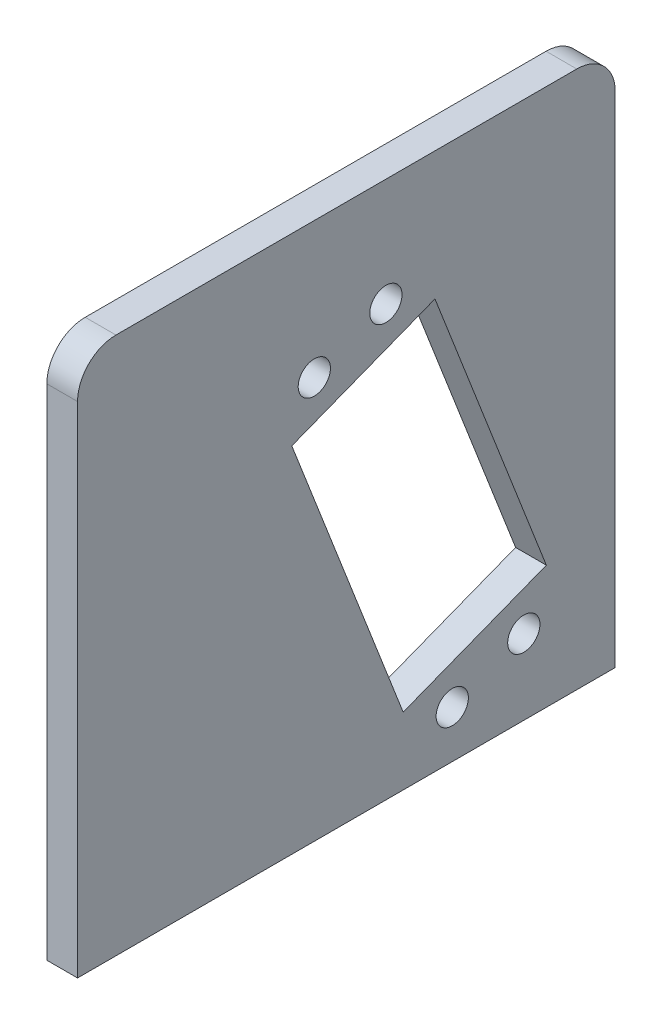
SolidWorks part; units mm, degrees
ref_plane "Front Plane" through (0, 0, 0) normal (0, 0, 1) x (1, 0, 0)
ref_plane "Top Plane" through (0, 0, 0) normal (0, 1, 0) x (1, 0, 0)
ref_plane "Right Plane" through (0, 0, 0) normal (1, 0, 0) x (0, 0, -1)
sketch "Sketch1" plane through (0, 0, 0) normal (0, 1, 0) x (1, 0, 0)
  line L5 (39.2287, 39.2125) -> (39.2287, -30.7875)
  line L9 (39.2287, 39.2125) -> (35.2287, 39.2125)
  line L10 (35.2287, 39.2125) -> (35.2287, -30.7875)
  line L11 (35.2287, -30.7875) -> (39.2287, -30.7875)
  dimension "D6" = 4
extrude "Boss-Extrude1" add sketch "Sketch1" along normal blind 3 contours L11 L10 L9 | L10 L11 L9 region at (37.2287, 0, -4.2125)
extrude "Boss-Extrude2" add sketch "Sketch1<3>" along normal blind 70
sketch "Sketch1<3>" plane through (0, 0, 0) normal (0, 1, 0) x (1, 0, 0) same geometry as "Sketch1"
extrude "Boss-Extrude3" add sketch "Sketch1<4>" along normal blind 70 rebuild error yes
sketch "Sketch1<4>" plane through (0, 0, 0) normal (0, 1, 0) x (1, 0, 0) same geometry as "Sketch1"
sketch "Sketch5" plane through (-50.7713, 0, 0) normal (-1, 0, 0) x (0, 0, 1)
  line L0 (-8.0225, 70) -> (-8.0225, 0) construction
  line L5 (-34.2125, 70) -> (-34.2125, 3) construction
  circle A0 centre (-8.0225, 60) radius 4
  dimension "D1" = 60
  dimension "D3" = 8
  dimension "D2" = 26.19
extrude "Cut-Extrude4" cut sketch "Sketch5" against normal blind 10 rebuild error yes
sketch "Sketch6" plane through (0, 3, 0) normal (0, 1, 0) x (1, 0, 0)
  line L0 (-50.7876, 44.2125) -> (49.2124, 44.2125) construction
  line L3 (-50.7876, -35.7875) -> (49.2124, -35.7875) construction
  line L8 (-50.7713, -40.7875) -> (39.2287, -40.7875) construction
  line L9 (-50.7713, 49.2125) -> (39.2287, 49.2125) construction
  circle A0 centre (-45.7876, -35.7875) radius 2.5
  circle A1 centre (-45.7876, 44.2125) radius 2.5
  circle A2 centre (43.7185, 44.2125) radius 2.5
  circle A3 centre (43.7185, -35.7875) radius 2.5
  dimension "D1" = 5
  dimension "D2" = 5
  dimension "D3" = 5
  dimension "D4" = 5
extrude "Cut-Extrude5" cut sketch "Sketch6" against normal blind 10 rebuild error yes
extrude "Boss-Extrude4" add sketch "Sketch1<5>" along normal blind 80 rebuild error yes
sketch "Sketch1<5>" plane through (0, 0, 0) normal (0, 1, 0) x (1, 0, 0) same geometry as "Sketch1"
extrude "Cut-Extrude6" cut sketch "Sketch5<2>" against normal blind 10 rebuild error yes
sketch "Sketch5<2>" plane through (-50.7713, 0, 0) normal (-1, 0, 0) x (0, 0, 1) same geometry as "Sketch5"
fillet "Fillet1" radius 3 rebuild error yes
fillet "Fillet2" radius 5 2 edges at (37.2287, 70, -39.2125) (37.2287, 70, 30.7875)
fillet "Fillet3" radius 4 rebuild error yes
sketch "Sketch7" plane through (39.2287, 0, 0) normal (1, 0, 0) x (0, 0, -1)
  line L0 (-30.7875, -10) -> (39.2125, -10) construction
  line L1 (-30.7875, 65) -> (-30.7875, 0) construction
  line L2 (39.2125, 65) -> (39.2125, 0) construction
  line L3 (-37.7875, 0) -> (46.2125, 0) construction
  circle A0 centre (27.4823, -10) radius 2.5
  dimension "D1" = 10
extrude "Cut-Extrude7" cut sketch "Sketch7" against normal blind 10 rebuild error yes
sketch "Sketch8" plane through (39.2287, 0, 0) normal (1, 0, 0) x (0, 0, -1)
  line L0 (39.2125, 20) -> (-30.7875, 20) construction
  line L1 (39.2125, 65) -> (39.2125, 0) construction
  line L2 (-30.7875, 65) -> (-30.7875, 0) construction
  line L3 (26.9146, 20) -> (8.0207, 38.8939) construction
  circle A0 centre (8.0207, 38.8939) radius 2.5
  dimension "D3" = 5
  dimension "D1" = 26.72
  dimension "D2" = 45
extrude "Cut-Extrude8" cut sketch "Sketch8" against normal blind 10
sketch "Sketch9" plane through (39.2287, 0, 0) normal (1, 0, 0) x (0, 0, -1)
  circle A1 centre (8.0207, 38.8939) radius 3.5
extrude "Cut-Extrude9" cut sketch "Sketch9" against normal up to surface (67.5 mm away) rebuild error yes
sketch "Sketch26" plane through (0, 3, 0) normal (0, 1, 0) x (1, 0, 0)
  line L0 (39.2287, 39.2125) -> (39.2287, 46.2125) construction
  line L1 (39.2287, -37.7875) -> (39.2287, -30.7875) construction
  circle A0 centre (34.2287, 44.2125) radius 2.5
  circle A2 centre (34.2287, -36.0634) radius 2.5
  dimension "D1" = 5
  dimension "D2" = 5
  dimension "D3" = 5
  dimension "D4" = 5
extrude "Cut-Extrude11" cut sketch "Sketch26" against normal blind 10 contours A2 | A0 rebuild error yes
sketch "Sketch27" plane through (0, 3, 0) normal (0, 1, 0) x (1, 0, 0)
  line L0 (-49.8926, 48.3339) -> (38.35, -39.9088) construction
  line L1 (38.35, 48.3339) -> (-49.8926, -39.9088) construction
  line L2 (7.7287, 4.2125) -> (-19.2713, 4.2125) construction
  line L3 (7.7287, 3.4625) -> (-19.2713, 3.4625)
  line L4 (7.7287, 4.9625) -> (-19.2713, 4.9625)
  line L5 (0.9787, -7.4788) -> (-12.5213, 15.9039) construction
  line L6 (0.3292, -7.8538) -> (-13.1708, 15.5289)
  line L7 (1.6282, -7.1038) -> (-11.8718, 16.2789)
  line L8 (-12.5213, -7.4788) -> (0.9787, 15.9039) construction
  line L9 (-13.1708, -7.1038) -> (0.3292, 16.2789)
  line L10 (-11.8718, -7.8538) -> (1.6282, 15.5289)
  line L11 (-19.2713, 4.2125) -> (7.7287, 4.2125) construction
  line L12 (-19.2713, 4.9625) -> (7.7287, 4.9625)
  line L13 (-19.2713, 3.4625) -> (7.7287, 3.4625)
  line L14 (-12.5213, 15.9039) -> (0.9787, -7.4788) construction
  line L15 (-11.8718, 16.2789) -> (1.6282, -7.1038)
  line L16 (-13.1708, 15.5289) -> (0.3292, -7.8538)
  line L17 (0.9787, 15.9039) -> (-12.5213, -7.4788) construction
  line L18 (1.6282, 15.5289) -> (-11.8718, -7.8538)
  line L19 (0.3292, 16.2789) -> (-13.1708, -7.1038)
  arc A0 (-47.7713, 49.2125) -> (-50.7713, 46.2125) centre (-47.7713, 46.2125) ccw construction
  arc A1 (36.2287, -40.7875) -> (39.2287, -37.7875) centre (36.2287, -37.7875) ccw construction
  arc A2 (39.2287, 46.2125) -> (36.2287, 49.2125) centre (36.2287, 46.2125) ccw construction
  arc A3 (-50.7713, -37.7875) -> (-47.7713, -40.7875) centre (-47.7713, -37.7875) ccw construction
  arc A4 (7.7287, 3.4625) -> (7.7287, 4.9625) centre (7.7287, 4.2125) ccw
  arc A5 (-19.2713, 4.9625) -> (-19.2713, 3.4625) centre (-19.2713, 4.2125) ccw
  circle A9 centre (-5.7713, 4.2125) radius 5.375
  arc A10 (0.3292, -7.8538) -> (1.6282, -7.1038) centre (0.9787, -7.4788) ccw
  arc A11 (-11.8718, 16.2789) -> (-13.1708, 15.5289) centre (-12.5213, 15.9039) ccw
  arc A12 (-13.1708, -7.1038) -> (-11.8718, -7.8538) centre (-12.5213, -7.4788) ccw
  arc A13 (1.6282, 15.5289) -> (0.3292, 16.2789) centre (0.9787, 15.9039) ccw
  arc A14 (-19.2713, 4.9625) -> (-19.2713, 3.4625) centre (-19.2713, 4.2125) ccw
  arc A15 (7.7287, 3.4625) -> (7.7287, 4.9625) centre (7.7287, 4.2125) ccw
  arc A16 (-11.8718, 16.2789) -> (-13.1708, 15.5289) centre (-12.5213, 15.9039) ccw
  arc A17 (0.3292, -7.8538) -> (1.6282, -7.1038) centre (0.9787, -7.4788) ccw
  arc A18 (1.6282, 15.5289) -> (0.3292, 16.2789) centre (0.9787, 15.9039) ccw
  arc A19 (-13.1708, -7.1038) -> (-11.8718, -7.8538) centre (-12.5213, -7.4788) ccw
  circle A20 centre (-5.7713, 4.2125) radius 2.75
  point P18 (-5.7713, 4.2125)
  point P30 (-5.7713, 4.2125)
  point P37 (-5.7713, 4.2125)
  point P44 (-5.7713, 4.2125)
  point P51 (-5.7713, 4.2125)
  point P58 (-5.7713, 4.2125)
  point P63 (-5.7713, 4.2125)
  dimension "D1" = 10.75
  dimension "D2" = 0.75
  dimension "D3" = 13.5
  dimension "D4" = 6
extrude "Cut-Extrude14" cut sketch "Sketch27" against normal blind 10 contours L3 A5 L4 A4 | L6 A11 L7 A10 | L10 A13 L9 A12 rebuild error yes
extrude "Cut-Extrude15" cut sketch "Sketch27<7>" against normal blind 10 contours L3 A20 L9 | L6 A20 L4 | L9 A20 L7 | L4 A20 L10 | L7 A20 L3 | L10 A20 L6 rebuild error yes
sketch "Sketch27<7>" plane through (0, 3, 0) normal (0, 1, 0) x (1, 0, 0) same geometry as "Sketch27"
sketch "Sketch28" plane through (-50.7713, 0, 0) normal (-1, 0, 0) x (0, 0, 1)
  line L0 (-23.4588, 51.635) -> (-8.5312, 68.47)
  line L1 (-8.5312, 68.47) -> (0.4475, 60.5086)
  line L2 (0.4475, 60.5086) -> (-14.4801, 43.6736)
  line L3 (-14.4801, 43.6736) -> (-23.4588, 51.635)
  line L4 (-8.0225, 60) -> (-12.6884, 54.7379) construction
  line L5 (-12.6884, 54.7379) -> (-25.2505, 40.5707) construction
  line L6 (-8.0225, 60) -> (2.1094, 71.4266) construction
  circle A0 centre (-8.0225, 60) radius 4 construction
  circle A1 centre (-8.0225, 60) radius 4
  circle A2 centre (-2.3169, 66.4347) radius 1
  circle A3 centre (-20.6944, 45.709) radius 1
  point P8 (-18.9694, 47.6543)
  dimension "D3" = 2
  dimension "D4" = 8.6
  dimension "D5" = 27.7
  dimension "D1" = 22.5
  dimension "D2" = 12
  dimension "D6" = 2.6
extrude "Cut-Extrude16" cut sketch "Sketch28" against normal up to surface (4 mm away) rebuild error yes
sketch "Sketch29" plane through (39.2287, 0, 0) normal (1, 0, 0) x (0, 0, -1)
  line L8 (8.0207, 38.8939) -> (0.0593, 47.8726) construction
  line L9 (0.0593, 47.8726) -> (61.0966, -20.9639) construction
  line L10 (11.5223, 50.0177) -> (38.0602, 20.0888)
  line L11 (38.0602, 20.0888) -> (23.0957, 6.8199)
  line L12 (23.0957, 6.8199) -> (-3.4422, 36.7487)
  line L13 (-3.4422, 36.7487) -> (11.5223, 50.0177)
  line L14 (11.5223, 50.0177) -> (23.0957, 6.8199) construction
  line L15 (38.0602, 20.0888) -> (-3.4422, 36.7487) construction
  line L16 (17.309, 28.4188) -> (24.2914, 34.6101) construction
  circle A0 centre (37.4771, 13.21) radius 2.1
  circle A1 centre (30.2988, 6.2479) radius 2.1
  circle A4 centre (-3.1481, 43.9685) radius 2.1
  circle A6 centre (8.0207, 38.8939) radius 3.5 construction
  circle A7 centre (8.0207, 38.8939) radius 3.5
  circle A10 centre (4.6231, 50.262) radius 2.1
  point P4 (4.04, 43.3832)
  point P28 (30.578, 13.4543)
  dimension "D4" = 5
  dimension "D5" = 10
  dimension "D6" = 4.76
  dimension "D1" = 4.2
  dimension "D2" = 20
  dimension "D3" = 40
sketch "Sketch31" plane through (0, 3, 0) normal (0, 1, 0) x (1, 0, 0)
  circle A0 centre (-5.7713, 4.2125) radius 5.375
  dimension "D1" = 10.75
extrude "Cut-Extrude19" cut sketch "Sketch31" against normal blind 10 rebuild error yes
sketch "Sketch33" plane through (39.2287, 0, 0) normal (1, 0, 0) x (0, 0, -1)
  circle A0 centre (8.0207, 38.8939) radius 3.5 construction
  circle A1 centre (8.0207, 38.8939) radius 3.5
sketch "Sketch35" plane through (39.2287, 0, 0) normal (1, 0, 0) x (0, 0, -1)
  line L0 (8.0207, 38.8939) -> (19.6601, 8.9793) construction
  line L1 (19.6601, 8.9793) -> (4.6231, 48.162) construction
  line L2 (-2.8922, 46.0528) -> (30.2509, 16.0273) construction
  line L3 (15.7466, 53.305) -> (30.2509, 16.0273)
  line L4 (30.2509, 16.0273) -> (11.612, 8.7751)
  line L5 (11.612, 8.7751) -> (-2.8922, 46.0528)
  line L6 (-2.8922, 46.0528) -> (15.7466, 53.305)
  line L7 (15.7466, 53.305) -> (11.612, 8.7751) construction
  line L8 (13.6793, 31.0401) -> (19.6601, 33.3671) construction
  circle A0 centre (8.0207, 38.8939) radius 3.5
  circle A1 centre (4.6231, 50.262) radius 2.1 construction
  circle A2 centre (-3.1481, 43.9685) radius 2.1 construction
  circle A3 centre (9.3609, 55.928) radius 2.1
  circle A4 centre (0.0415, 52.3019) radius 2.1
  circle A5 centre (27.3172, 9.7782) radius 2.1
  circle A6 centre (17.9977, 6.1521) radius 2.1
  point P3 (13.6793, 31.0401)
  dimension "D4" = 4.2
  dimension "D6" = 10
  dimension "D7" = 4.76
  dimension "D1" = 20
  dimension "D2" = 40
  dimension "D3" = 9.68
  dimension "D5" = 5
  dimension "D8" = 4.76
  dimension "D9" = 15
  dimension "D10" = 5
  dimension "D11" = 40
  dimension "D12" = 20
extrude "Cut-Extrude20" cut sketch "Sketch35" against normal blind 10
sketch "Sketch36" plane through (39.2287, 0, 0) normal (1, 0, 0) x (0, 0, -1)
  circle A0 centre (8.0207, 38.8939) radius 5.1031
extrude "Cut-Extrude21" cut sketch "Sketch36" against normal blind 10
